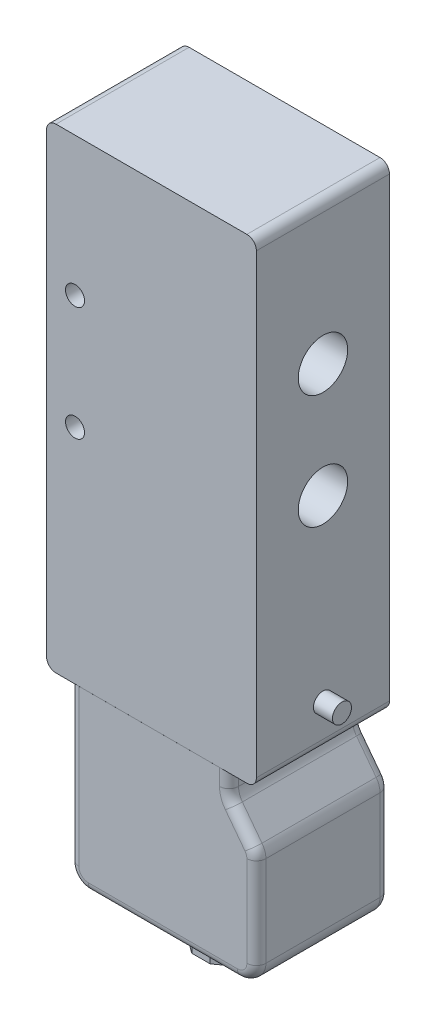
SolidWorks part; units mm, degrees
ref_plane "Front Plane" through (0, 0, 0) normal (0, 0, 1) x (1, 0, 0)
ref_plane "Top Plane" through (0, 0, 0) normal (0, 1, 0) x (1, 0, 0)
ref_plane "Right Plane" through (0, 0, 0) normal (1, 0, 0) x (0, 0, -1)
sketch "Sketch2" plane through (0, 0, 0) normal (0, 0, 1) x (1, 0, 0)
  line L1 (0, 0) -> (35.052, 0)
  line L2 (0, 0) -> (0, 79.375)
  line L3 (0, 79.375) -> (35.052, 79.375)
  line L4 (35.052, 0) -> (35.052, 79.375)
extrude "Boss-Extrude1" add sketch "Sketch2" along normal blind 22.225
sketch "Sketch3" plane through (35.052, 0, 0) normal (1, 0, 0) x (0, 0, -1)
  line L4 (0, 0) -> (0, 79.375)
  line L5 (0, 79.375) -> (-22.225, 79.375)
  line L6 (-22.225, 79.375) -> (-22.225, 0)
  line L7 (-22.225, 0) -> (0, 0)
  line L8 (0, 0) -> (0, 79.375)
  line L9 (0, 79.375) -> (-22.225, 79.375)
  line L10 (-22.225, 79.375) -> (-22.225, 0)
  line L11 (-22.225, 0) -> (0, 0)
  circle A0 centre (-11.1125, 6.985) radius 1.5875
  dimension "D2" = 11.1125
  dimension "D4" = 3.175
  dimension "D3" = 6.985
  dimension "D1" = 0
extrude "Boss-Extrude2" add sketch "Sketch3" along normal blind 3.175 contours A0 region at (35.052, 6.985, 11.1125)
sketch "Sketch4" plane through (0, 0, 22.225) normal (0, 0, 1) x (1, 0, 0)
  line L0 (35.052, 0) -> (35.052, 79.375) construction
  line L1 (35.052, 79.375) -> (0, 79.375) construction
  line L2 (0, 0) -> (35.052, 0) construction
  line L3 (0, 79.375) -> (0, 0) construction
  line L4 (35.052, 0) -> (35.052, 79.375)
  line L5 (35.052, 79.375) -> (0, 79.375)
  line L6 (0, 0) -> (35.052, 0)
  line L7 (0, 79.375) -> (0, 0)
  line L8 (0, 0) -> (3.81, 0)
  line L9 (3.81, 0) -> (29.21, 0)
  line L10 (35.052, 0) -> (3.81, 0)
  line L11 (35.052, 0) -> (35.052, -29.21)
  line L12 (35.052, -29.21) -> (3.81, -29.21)
  line L13 (3.81, 0) -> (3.81, -29.21)
  line L14 (3.81, 0) -> (29.21, 0)
  line L15 (29.21, 0) -> (30.48, 0)
  line L16 (30.48, 0) -> (30.48, -3.81)
  line L17 (30.48, -3.81) -> (35.052, -9.8361)
  line M2 (0, 0) -> (35.052, 0)
extrude "Boss-Extrude4" add sketch "Sketch4" against normal up to surface (22.225 mm away) contours L17 L16 L6 L13 L12 L11 M2 region at (18.9471, -14.9933, 22.225) up to face at (17.526, 39.6875, 0)
fillet "Fillet2" radius 3.175 4 edges at (3.81, -29.21, 11.1125) (30.48, -3.81, 11.1125) (35.052, -9.8361, 11.1125) (35.052, -29.21, 11.1125)
sketch "Sketch5" plane through (0, 0, 22.225) normal (0, 0, 1) x (1, 0, 0)
  line L0 (3.81, 0) -> (30.48, 0)
  line L10 (3.81, 0) -> (3.81, -26.035)
  line L11 (6.985, -29.21) -> (31.877, -29.21)
  line L12 (35.052, -26.035) -> (35.052, -10.9042)
  line L13 (34.4064, -8.9852) -> (31.1256, -4.6609)
  line L14 (30.48, -2.7419) -> (30.48, 0)
  line L15 (30.48, 0) -> (35.052, 0)
  line L16 (35.052, 0) -> (35.052, 79.375)
  line L17 (35.052, 79.375) -> (0, 79.375)
  line L18 (0, 79.375) -> (0, 0)
  line L19 (0, 0) -> (3.81, 0)
  line L20 (3.81, 0) -> (3.81, -26.035)
  line L21 (6.985, -29.21) -> (31.877, -29.21)
  line L22 (35.052, -26.035) -> (35.052, -10.9042)
  line L23 (34.4064, -8.9852) -> (31.1256, -4.6609)
  line L24 (30.48, -2.7419) -> (30.48, 0)
  line L25 (30.48, 0) -> (35.052, 0)
  line L26 (35.052, 0) -> (35.052, 79.375)
  line L27 (35.052, 79.375) -> (0, 79.375)
  line L28 (0, 79.375) -> (0, 0)
  line L29 (0, 0) -> (3.81, 0)
  arc A4 (3.81, -26.035) -> (6.985, -29.21) centre (6.985, -26.035) ccw
  arc A5 (31.877, -29.21) -> (35.052, -26.035) centre (31.877, -26.035) ccw
  arc A6 (35.052, -10.9042) -> (34.4064, -8.9852) centre (31.877, -10.9042) ccw
  arc A7 (30.48, -2.7419) -> (31.1256, -4.6609) centre (33.655, -2.7419) ccw
  arc A8 (3.81, -26.035) -> (6.985, -29.21) centre (6.985, -26.035) ccw
  arc A9 (31.877, -29.21) -> (35.052, -26.035) centre (31.877, -26.035) ccw
  arc A10 (35.052, -10.9042) -> (34.4064, -8.9852) centre (31.877, -10.9042) ccw
  arc A11 (30.48, -2.7419) -> (31.1256, -4.6609) centre (33.655, -2.7419) ccw
  line M15 (3.81, 0) -> (3.81, -26.035)
  arc M16 (3.81, -26.035) -> (6.985, -29.21) centre (6.985, -26.035) ccw
  line M17 (6.985, -29.21) -> (31.877, -29.21)
  arc M18 (31.877, -29.21) -> (35.052, -26.035) centre (31.877, -26.035) ccw
  line M19 (35.052, -26.035) -> (35.052, -10.9042)
  arc M20 (35.052, -10.9042) -> (34.4064, -8.9852) centre (31.877, -10.9042) ccw
  line M21 (34.4064, -8.9852) -> (31.1256, -4.6609)
  arc M22 (31.1256, -4.6609) -> (30.48, -2.7419) centre (33.655, -2.7419) cw
  line M23 (30.48, -2.7419) -> (30.48, 0)
  dimension "D1" = 0
extrude "Boss-Extrude5" add sketch "Sketch5" along normal blind 0.0025 contours L0 M15 M16 M17 M18 M19 M20 M21 M22 M23 region at (18.9441, -14.9259, 22.225)
sketch "Sketch6" plane through (0, 0, 0) normal (0, 0, -1) x (-1, 0, 0)
  line L0 (-30.48, 0) -> (-3.81, 0)
  line L10 (-31.877, -29.21) -> (-6.985, -29.21)
  line L11 (-3.81, -26.035) -> (-3.81, 0)
  line L12 (-3.81, 0) -> (0, 0)
  line L13 (0, 0) -> (0, 79.375)
  line L14 (0, 79.375) -> (-35.052, 79.375)
  line L15 (-35.052, 79.375) -> (-35.052, 0)
  line L16 (-35.052, 0) -> (-30.48, 0)
  line L17 (-30.48, 0) -> (-30.48, -2.7419)
  line L18 (-31.1256, -4.6609) -> (-34.4064, -8.9852)
  line L19 (-35.052, -10.9042) -> (-35.052, -26.035)
  line L20 (-31.877, -29.21) -> (-6.985, -29.21)
  line L21 (-3.81, -26.035) -> (-3.81, 0)
  line L22 (-3.81, 0) -> (0, 0)
  line L23 (0, 0) -> (0, 79.375)
  line L24 (0, 79.375) -> (-35.052, 79.375)
  line L25 (-35.052, 79.375) -> (-35.052, 0)
  line L26 (-35.052, 0) -> (-30.48, 0)
  line L27 (-30.48, 0) -> (-30.48, -2.7419)
  line L28 (-31.1256, -4.6609) -> (-34.4064, -8.9852)
  line L29 (-35.052, -10.9042) -> (-35.052, -26.035)
  arc A4 (-6.985, -29.21) -> (-3.81, -26.035) centre (-6.985, -26.035) ccw
  arc A5 (-31.1256, -4.6609) -> (-30.48, -2.7419) centre (-33.655, -2.7419) ccw
  arc A6 (-34.4064, -8.9852) -> (-35.052, -10.9042) centre (-31.877, -10.9042) ccw
  arc A7 (-35.052, -26.035) -> (-31.877, -29.21) centre (-31.877, -26.035) ccw
  arc A8 (-6.985, -29.21) -> (-3.81, -26.035) centre (-6.985, -26.035) ccw
  arc A9 (-31.1256, -4.6609) -> (-30.48, -2.7419) centre (-33.655, -2.7419) ccw
  arc A10 (-34.4064, -8.9852) -> (-35.052, -10.9042) centre (-31.877, -10.9042) ccw
  arc A11 (-35.052, -26.035) -> (-31.877, -29.21) centre (-31.877, -26.035) ccw
  line M15 (-31.877, -29.21) -> (-6.985, -29.21)
  arc M16 (-6.985, -29.21) -> (-3.81, -26.035) centre (-6.985, -26.035) ccw
  line M17 (-3.81, -26.035) -> (-3.81, 0)
  line M23 (-30.48, 0) -> (-30.48, -2.7419)
  arc M24 (-30.48, -2.7419) -> (-31.1256, -4.6609) centre (-33.655, -2.7419) cw
  line M25 (-31.1256, -4.6609) -> (-34.4064, -8.9852)
  arc M26 (-34.4064, -8.9852) -> (-35.052, -10.9042) centre (-31.877, -10.9042) ccw
  line M27 (-35.052, -10.9042) -> (-35.052, -26.035)
  arc M28 (-35.052, -26.035) -> (-31.877, -29.21) centre (-31.877, -26.035) ccw
  dimension "D1" = 0
extrude "Boss-Extrude6" add sketch "Sketch6" along normal blind 0.0025 contours L0 M23 M24 M25 M26 M27 M28 M15 M16 M17 region at (18.9441, -14.9259, 0)
sketch "Sketch7" plane through (0, -29.21, 0) normal (0, -1, 0) x (1, 0, 0)
  line L1 (31.877, -0.0025) -> (6.985, -0.0025)
  line L2 (31.877, -0.0025) -> (31.877, 22.2275)
  line L3 (31.877, 22.2275) -> (6.985, 22.2275)
  line L4 (31.877, -0.0025) -> (31.877, 22.2275)
  line L5 (31.877, 22.2275) -> (6.985, 22.2275)
  line L6 (6.985, 22.2275) -> (6.985, -0.0025)
  line L7 (6.985, -0.0025) -> (31.877, -0.0025)
  line L8 (31.877, -0.0025) -> (31.877, 22.2275)
  line L9 (31.877, 22.2275) -> (6.985, 22.2275)
  line L10 (6.985, 22.2275) -> (6.985, -0.0025)
  line L11 (6.985, -0.0025) -> (31.877, -0.0025)
  line L12 (6.985, -0.0025) -> (6.985, 22.2275)
  line L13 (31.877, -0.0025) -> (6.985, -0.0025)
  line L14 (31.877, -0.0025) -> (31.877, 22.2275)
  line L15 (31.877, 22.2275) -> (6.985, 22.2275)
  line L16 (6.985, -0.0025) -> (6.985, 22.2275)
  line L17 (14.4462, 11.1125) -> (15.3983, 8.1825)
  line L18 (15.3983, 8.1825) -> (17.8906, 6.3717)
  line L19 (17.8906, 6.3717) -> (20.9714, 6.3717)
  line L20 (20.9714, 6.3717) -> (23.4637, 8.1825)
  line L21 (23.4637, 8.1825) -> (24.4157, 11.1125)
  line L22 (24.4157, 11.1125) -> (23.4637, 14.0425)
  line L23 (23.4637, 14.0425) -> (20.9714, 15.8533)
  line L24 (20.9714, 15.8533) -> (17.8906, 15.8533)
  line L25 (17.8906, 15.8533) -> (15.3983, 14.0425)
  line L26 (15.3983, 14.0425) -> (14.4462, 11.1125)
  circle A0 centre (19.431, 11.1125) radius 4.9848
  circle A1 centre (19.431, 11.1125) radius 4.9848 construction
  dimension "D1" = 0
extrude "Boss-Extrude7" add sketch "Sketch7" along normal blind 6.35 contours L25 L26 L17 L18 L19 L20 L21 L22 L23 L24 region at (19.431, -29.21, 11.1125)
sketch "Sketch8" plane through (0, -29.21, 0) normal (0, -1, 0) x (1, 0, 0)
  line L1 (31.877, -0.0025) -> (6.985, -0.0025)
  line L2 (31.877, -0.0025) -> (31.877, 22.2275)
  line L3 (31.877, 22.2275) -> (6.985, 22.2275)
  line L4 (31.877, -0.0025) -> (31.877, 22.2275)
  line L5 (31.877, 22.2275) -> (6.985, 22.2275)
  line L6 (6.985, 22.2275) -> (6.985, -0.0025)
  line L7 (6.985, -0.0025) -> (31.877, -0.0025)
  line L8 (31.877, -0.0025) -> (31.877, 22.2275)
  line L9 (31.877, 22.2275) -> (6.985, 22.2275)
  line L10 (6.985, 22.2275) -> (6.985, -0.0025)
  line L11 (6.985, -0.0025) -> (31.877, -0.0025)
  line L12 (6.985, -0.0025) -> (6.985, 22.2275)
  circle A0 centre (19.431, 11.1125) radius 3.175
  circle A1 centre (19.431, 11.1125) radius 7.4412
  line M9 (15.3983, 14.0425) -> (17.8906, 15.8533)
  line M10 (17.8906, 15.8533) -> (20.9714, 15.8533)
  line M11 (20.9714, 15.8533) -> (23.4637, 14.0425)
  line M12 (23.4637, 14.0425) -> (24.4157, 11.1125)
  line M13 (24.4157, 11.1125) -> (23.4637, 8.1825)
  line M14 (23.4637, 8.1825) -> (20.9714, 6.3717)
  line M15 (20.9714, 6.3717) -> (17.8906, 6.3717)
  line M16 (17.8906, 6.3717) -> (15.3983, 8.1825)
  line M17 (15.3983, 8.1825) -> (14.4462, 11.1125)
  line M18 (14.4462, 11.1125) -> (15.3983, 14.0425)
  dimension "D1" = 0
extrude "Cut-Extrude2" cut sketch "Sketch8" along normal blind 1.5875 contours A1 M18 M9 M10 M11 M12 M13 M14 M15 M16 M17 | A0 M9 M18 M17 M16 M15 M14 M13 M12 M11 M10 region at (12.2003, -29.21, 11.1125) region at (16.7253, -29.21, 14.8366)
fillet "Fillet3" radius 1.5875 4 edges at (0, 79.375, 11.1125) (0, 0, 11.1125) (35.052, 0, 11.1125) (35.052, 79.375, 11.1125)
fillet "Fillet5" radius 1.5875 11 edges at (4.7399, -28.2801, -0.0025) (34.1221, -28.2801, -0.0025) (34.8863, -9.8919, -0.0025) (30.6457, -3.7542, -0.0025) (34.1221, -28.2801, 22.2275) (35.052, -18.4696, 22.2275) (34.8863, -9.8919, 22.2275) (30.6457, -3.7542, 22.2275) (30.48, -1.3709, 22.2275) (4.7399, -28.2801, 22.2275) (3.81, -13.0175, 22.2275)
sketch "Sketch9" plane through (35.052, 0, 0) normal (1, 0, 0) x (0, 0, -1)
  line L0 (0, 77.7875) -> (-22.225, 77.7875)
  line L1 (0, 77.7875) -> (-22.225, 77.7875)
  line L2 (-22.225, 79.375) -> (0, 79.375) construction
  line L4 (-22.225, 77.7875) -> (-22.225, 1.5875)
  line L5 (-22.225, 1.5875) -> (0, 1.5875)
  line L6 (0, 1.5875) -> (0, 77.7875)
  line L7 (0, 77.7875) -> (-22.225, 77.7875)
  line L8 (-22.225, 77.7875) -> (-22.225, 1.5875)
  line L9 (-22.225, 1.5875) -> (0, 1.5875)
  line L10 (0, 1.5875) -> (0, 77.7875)
  line L11 (0, 77.7875) -> (-22.225, 77.7875)
  circle A0 centre (-11.1125, 55.88) radius 4.1275
  circle A1 centre (-11.1125, 36.83) radius 4.1275
  point P6 (-11.1125, 77.7875)
  point P11 (0, 0)
  dimension "D2" = 8.255
  dimension "D3" = 23.495
  dimension "D4" = 19.05
  dimension "D1" = 0
extrude "Cut-Extrude3" cut sketch "Sketch9" against normal blind 6.858 contours A0 | A1 region at (35.052, 55.88, 11.1125) region at (35.052, 36.83, 11.1125)
sketch "Sketch10" plane through (0, 0, 0) normal (-1, 0, 0) x (0, 0, 1)
  line L0 (0, 79.375) -> (22.225, 79.375) construction
  line L1 (0, 79.375) -> (22.225, 79.375)
  line L2 (11.1125, 79.375) -> (11.1125, 69.85)
  line L3 (11.1125, 69.85) -> (11.1125, 65.7225)
  line L4 (22.225, 1.5875) -> (22.225, 77.7875)
  line L5 (22.225, 77.7875) -> (0, 77.7875)
  line L6 (0, 77.7875) -> (0, 1.5875)
  line L7 (0, 1.5875) -> (22.225, 1.5875)
  line L8 (22.225, 1.5875) -> (22.225, 77.7875)
  line L9 (22.225, 77.7875) -> (0, 77.7875)
  line L10 (0, 77.7875) -> (0, 1.5875)
  line L11 (0, 1.5875) -> (22.225, 1.5875)
  line L14 (22.225, 0) -> (22.225, 1.5875)
  line L15 (22.225, 1.5875) -> (0, 1.5875)
  line L16 (0, 1.5875) -> (0, 0)
  line L17 (0, 0) -> (22.225, 0)
  line L18 (22.225, 0) -> (22.225, 1.5875)
  line L19 (22.225, 1.5875) -> (0, 1.5875)
  line L20 (0, 1.5875) -> (0, 0)
  line L21 (0, 0) -> (22.225, 0)
  circle A3 centre (11.1125, 65.7225) radius 4.1275
  circle A4 centre (11.1125, 46.6725) radius 4.1275
  circle A5 centre (11.1125, 27.6225) radius 4.1275
  dimension "D3" = 19.05
  dimension "D4" = 19.05
  dimension "D1" = 0
  dimension "D2" = 0
extrude "Cut-Extrude4" cut sketch "Sketch10" against normal blind 6.858 contours A3 | A4 | A5 region at (0, 68.5585, 13.9485) region at (0, 46.6725, 11.1125) region at (0, 27.6225, 11.1125)
sketch "Sketch11" plane through (0, 0, 22.225) normal (0, 0, 1) x (1, 0, 0)
  line L0 (0, 79.375) -> (0, 69.85)
  line L1 (0, 69.85) -> (0, 65.7225)
  line L2 (0, 65.7225) -> (0, 46.6725)
  line L3 (0, 46.6725) -> (0, 27.6225)
  line L4 (0, 27.6225) -> (0, 37.1475)
  line L5 (0, 37.1475) -> (3.175, 37.1475)
  line L6 (33.4645, 79.375) -> (1.5875, 79.375)
  line L7 (0, 77.7875) -> (0, 1.5875)
  line L8 (1.5875, 0) -> (5.3077, 0)
  line L9 (5.3077, 0) -> (28.9823, 0)
  line L10 (28.9823, 0) -> (33.4645, 0)
  line L11 (35.052, 1.5875) -> (35.052, 77.7875)
  line L12 (33.4645, 79.375) -> (1.5875, 79.375)
  line L13 (0, 77.7875) -> (0, 1.5875)
  line L14 (1.5875, 0) -> (5.3077, 0)
  line L15 (5.3077, 0) -> (28.9823, 0)
  line L16 (28.9823, 0) -> (33.4645, 0)
  line L17 (35.052, 1.5875) -> (35.052, 77.7875)
  line L18 (0, 46.6725) -> (0, 56.1975)
  line L19 (0, 56.1975) -> (3.175, 56.1975)
  circle A0 centre (4.7625, 56.1975) radius 1.5875
  circle A1 centre (4.7625, 37.1475) radius 1.5875
  arc A4 (1.5875, 79.375) -> (0, 77.7875) centre (1.5875, 77.7875) ccw
  arc A5 (0, 1.5875) -> (1.5875, 0) centre (1.5875, 1.5875) ccw
  arc A6 (33.4645, 0) -> (35.052, 1.5875) centre (33.4645, 1.5875) ccw
  arc A7 (35.052, 77.7875) -> (33.4645, 79.375) centre (33.4645, 77.7875) ccw
  arc A8 (1.5875, 79.375) -> (0, 77.7875) centre (1.5875, 77.7875) ccw
  arc A9 (0, 1.5875) -> (1.5875, 0) centre (1.5875, 1.5875) ccw
  arc A10 (33.4645, 0) -> (35.052, 1.5875) centre (33.4645, 1.5875) ccw
  arc A11 (35.052, 77.7875) -> (33.4645, 79.375) centre (33.4645, 77.7875) ccw
  dimension "D4" = 3.175
  dimension "D5" = 3.175
  dimension "D2" = 3.175
  dimension "D3" = 3.175
  dimension "D1" = 0
extrude "Cut-Extrude5" cut sketch "Sketch11" against normal through all contours A0 | A1 region at (4.7625, 56.1975, 22.225) region at (4.7625, 37.1475, 22.225)
